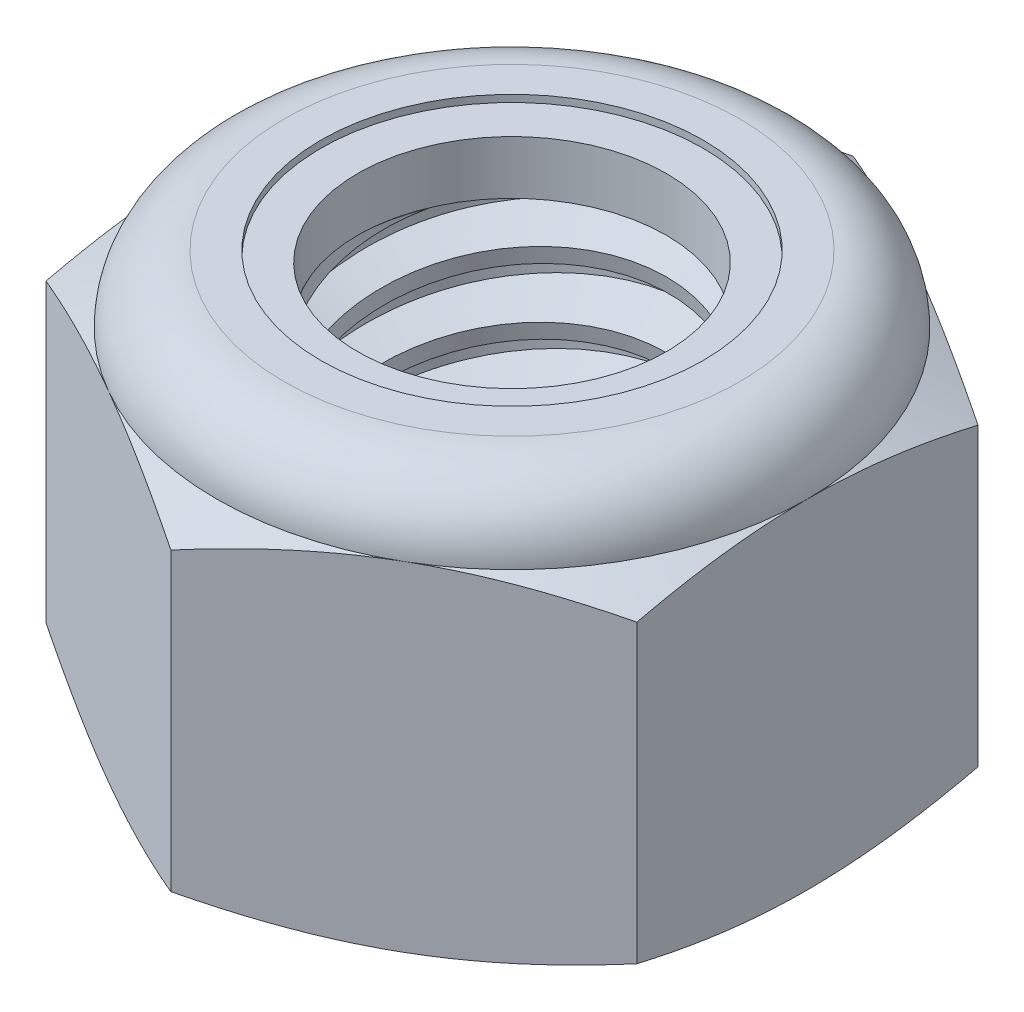
SolidWorks part; units mm, degrees
ref_plane "Front" through (0, 0, 0) normal (0, 0, 1) x (1, 0, 0)
ref_plane "Top" through (0, 0, 0) normal (0, 1, 0) x (1, 0, 0)
ref_plane "Right" through (0, 0, 0) normal (1, 0, 0) x (0, 0, -1)
sketch "Sketch1" plane through (0, 0, 0) normal (0, 1, 0) x (1, 0, 0)
  line L1 (0, 7.3323) -> (-6.35, 3.6662)
  line L2 (-6.35, 3.6662) -> (-6.35, -3.6662)
  line L3 (-6.35, -3.6662) -> (0, -7.3323)
  line L4 (0, -7.3323) -> (6.35, -3.6662)
  line L5 (6.35, -3.6662) -> (6.35, 3.6662)
  line L6 (6.35, 3.6662) -> (0, 7.3323)
  circle A0 centre (0, 0) radius 6.35 construction
  dimension "Hex Flats" = 12.7
extrude "Extrude1" add sketch "Sketch1" along normal blind 8.7312
sketch "Sketch2" plane through (0, 0, 0) normal (1, 0, 0) x (0, 0, -1)
  line L0 (-3.9624, 0) -> (-3.9624, 8.7312) construction
  line L1 (0, 0) -> (3.9624, 0)
  line L2 (0, 0) -> (0, 8.7312)
  line L3 (0, 8.7312) -> (3.9624, 8.7312)
  line L4 (3.9624, 0) -> (3.9624, 8.7312)
  line L5 (-3.6662, 8.7312) -> (3.6662, 8.7312) construction
  line L7 (0, -3.9624) -> (0, 0) construction
  dimension "Thread Dia" = 7.9248
revolve "Revolve1" add sketch "Sketch2" angle 360 about L7
sketch "Sketch3" plane through (0, 0, 0) normal (1, 0, 0) x (0, 0, -1)
  line L0 (3.9624, 8.7312) -> (-3.9624, 8.7312) construction
  line L1 (-3.9624, 8.7312) -> (-3.9624, 7.3201) construction
  line L2 (-3.9624, 7.3201) -> (3.9624, 8.7312) construction
  line L3 (3.9624, 8.7312) -> (3.9933, 8.5576) construction
  line L4 (3.9933, 8.5576) -> (4.2098, 7.342)
  line L5 (4.2098, 7.342) -> (3.3805, 7.6422)
  line L6 (3.3805, 7.6422) -> (3.3187, 7.9896)
  line L7 (3.3187, 7.9896) -> (3.9933, 8.5576)
  line L8 (3.3496, 7.8159) -> (4.1015, 7.9498) construction
  line L9 (3.9624, 8.7312) -> (3.9624, 7.925) construction
  line L10 (3.9624, 7.925) -> (-3.9624, 6.5139) construction
  line L11 (-3.9624, 6.5139) -> (-3.9624, 7.3201) construction
  line L12 (-0.2692, 8.7312) -> (0.2692, 5.7077) construction
  line L13 (-3.9624, 0) -> (-3.9624, 8.7312) construction
  line L14 (0, 8.7312) -> (3.9624, 8.7312) construction
  line L15 (3.9624, 0) -> (3.9624, 8.7312) construction
  point P13 (0, 7.2195)
  dimension "D1" = 0.1764
  dimension "D2" = 0.3528
  dimension "Thread Pitch" = 1.4111
  dimension "D4" = 60
  dimension "D5" = 1.4111
revolve "Cut-Revolve1" cut sketch "Sketch3" angle 360 about L12
pattern_linear "LPattern1" count 6 spacing 1.4111 along (0, -1, 0) count 2 spacing 1.4111 along (0, 1, 0) of "Cut-Revolve1"
sketch "Sketch4" plane through (0, 0, 0) normal (1, 0, 0) x (0, 0, -1)
  line L0 (0, 8.7312) -> (3.9624, 8.7312)
  line L1 (3.9624, 8.7312) -> (3.3187, 8.4311)
  line L2 (3.3187, 8.4311) -> (3.3187, 0.3002)
  line L3 (3.3187, 0.3002) -> (3.9624, 0)
  line L4 (3.9624, 0) -> (0, 0)
  line L5 (0, 0) -> (0, 8.7312)
  line L6 (3.9624, 0) -> (3.9624, 8.7312) construction
  line L7 (0, 8.7312) -> (3.9624, 8.7312) construction
  line L8 (0, 0) -> (3.9624, 0) construction
  line L9 (0, 0) -> (0, 8.7312) construction
  line L10 (0, 8.7312) -> (0, 9.4415) construction
  dimension "D1" = 25
revolve "Cut-Revolve2" cut sketch "Sketch4" angle 360 about L10
combine bodies "Combine1" operation type subtract main body 112 bodies to subtract 111
sketch "Sketch5" plane through (0, 0, 0) normal (1, 0, 0) x (0, 0, -1)
  line L0 (0, 0) -> (6.35, 0)
  line L1 (6.35, 0) -> (7.3323, 0.4581)
  line L2 (7.3323, 0.4581) -> (7.3323, 6.818)
  line L3 (7.3323, 6.818) -> (6.35, 7.276)
  line L4 (4.8948, 8.7312) -> (4.8948, 10.0012)
  line L5 (4.8948, 10.0012) -> (8.6023, 10.0012)
  line L6 (8.6023, 10.0012) -> (8.6023, -1.27)
  line L7 (8.6023, -1.27) -> (0, -1.27)
  line L8 (0, -1.27) -> (0, 0)
  line L9 (6.35, 7.276) -> (6.35, 0) construction
  line L10 (0, 0) -> (3.9624, 0) construction
  line L13 (7.3323, 3.638) -> (8.6023, 3.638) construction
  line L14 (7.3323, 8.7312) -> (7.3323, 0) construction
  line L15 (0, 0) -> (0, 10.0012) construction
  line L20 (0, 10.0012) -> (4.8948, 10.0012) construction
  line L22 (0, 8.7312) -> (3.9624, 8.7312) construction
  arc A0 (6.35, 7.276) -> (4.8948, 8.7312) centre (4.8948, 7.276) ccw
  dimension "D1" = 25
  dimension "D2" = 1.27
  dimension "D3" = 8.7312
  dimension "D4" = 1.4552
revolve "Cut-Revolve3" cut sketch "Sketch5" angle 360 about L15
sketch "Sketch6" plane through (0, 0, 0) normal (1, 0, 0) x (0, 0, -1)
  line L0 (0, 7.276) -> (6.1976, 7.276)
  line L1 (4.8948, 8.5788) -> (4.1067, 8.5788)
  line L2 (0, 10.0012) -> (0, 7.276)
  line L3 (4.1067, 10.0012) -> (0, 10.0012)
  line L4 (0, 10.0012) -> (4.8948, 10.0012) construction
  line L5 (0, 0) -> (0, 10.0012) construction
  line L6 (0, 10.0012) -> (0, 44.323) construction
  line L7 (4.1067, 8.5788) -> (4.1067, 10.0012)
  line L8 (4.8948, 8.7312) -> (4.8948, 8.5788) construction
  line L9 (4.1067, 8.5788) -> (3.3187, 8.5788) construction
  line L10 (3.3187, 8.5788) -> (3.3187, 8.4311) construction
  arc A0 (6.1976, 7.276) -> (4.8948, 8.5788) centre (4.8948, 7.276) ccw
  arc A1 (6.35, 7.276) -> (4.8948, 8.7312) centre (4.8948, 7.276) ccw construction
  dimension "D1" = 0.1524
revolve "Cut-Revolve4" cut sketch "Sketch6" angle 360 about L6
sketch "Sketch7" plane through (0, 0, 0) normal (1, 0, 0) x (0, 0, -1)
  line L0 (3.3187, 7.3522) -> (6.119, 7.3522)
  line L1 (4.8948, 8.5026) -> (3.3187, 8.5026)
  line L2 (3.3187, 8.5026) -> (3.3187, 7.3522)
  line L3 (3.3187, 7.3522) -> (0, 7.3522) construction
  line L4 (0, 7.3522) -> (0, 8.5026) construction
  line L5 (0, 8.5026) -> (3.3187, 8.5026) construction
  line L6 (3.3187, 7.3522) -> (3.3187, 7.276) construction
  line L7 (0, 7.276) -> (6.1976, 7.276) construction
  line L8 (4.8948, 8.5026) -> (4.8948, 8.5788) construction
  arc A0 (6.119, 7.3522) -> (4.8948, 8.5026) centre (4.8948, 7.276) ccw
  arc A2 (6.1976, 7.276) -> (4.8948, 8.5788) centre (4.8948, 7.276) ccw construction
  dimension "D1" = 0.0762
revolve "Revolve2" add sketch "Sketch7" angle 360 about L4
equation "\"D1@Sketch3\"=\"Thread Pitch@Sketch3\"/8"
equation "\"D2@Sketch3\"=\"Thread Pitch@Sketch3\"/4"
equation "\"D5@Sketch3\"=\"Thread Pitch@Sketch3\""
equation "\"D4@LPattern1\"=\"Thread Pitch@Sketch3\""
equation "\"D3@LPattern1\"=\"Thread Pitch@Sketch3\""
equation "\"D1@LPattern1\"=\"Height@Extrude1\"/\"Thread Pitch@Sketch3\""
equation "\"D4@Sketch5\"=\"Height@Extrude1\"/6"
